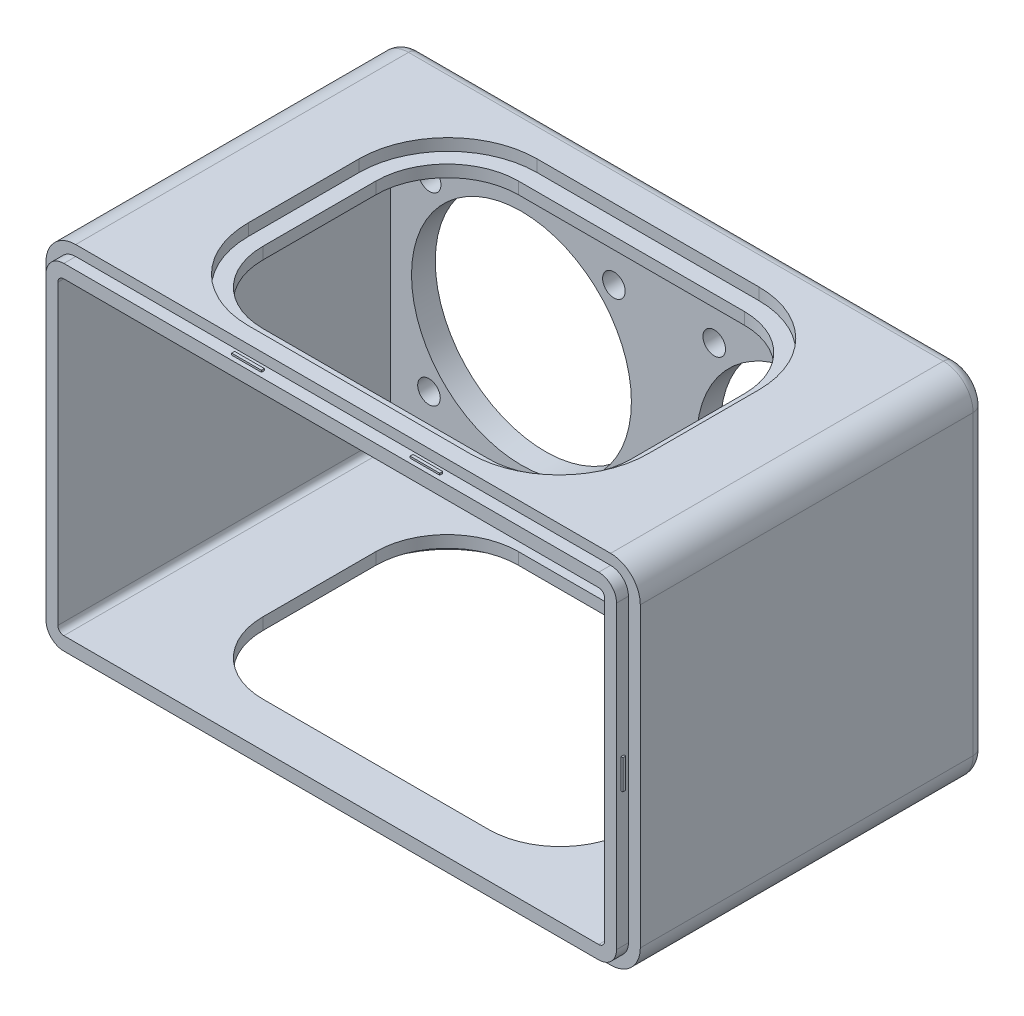
SolidWorks part; units mm, degrees
ref_plane "前视基准面" through (0, 0, 0) normal (0, 0, 1) x (1, 0, 0)
ref_plane "上视基准面" through (0, 0, 0) normal (0, 1, 0) x (1, 0, 0)
ref_plane "右视基准面" through (0, 0, 0) normal (1, 0, 0) x (0, 0, -1)
other "Configuration Table"
sketch "草图1" plane through (0, 0, 0) normal (0, 0, 1) x (1, 0, 0)
  line L0 (0, 0.156) -> (-70, 0.156) construction
  line L6 (-50, 30) -> (50, 30)
  line L11 (-50, 30) -> (-50, -30)
  line L12 (-50, -30) -> (50, -30)
  line L13 (50, 30) -> (50, -30)
  line L22 (-50, 30) -> (50, -30) construction
  line L23 (-50, -30) -> (50, 30) construction
  point P0 (0, 0)
  point P1 (0, 0)
  point P18 (0, 0)
  point P41 (0, 0)
  dimension "D1" = 100
  dimension "D2" = 60
extrude "凸台-拉伸2" add sketch "草图1" along normal blind 60
fillet "圆角1" radius 5 4 edges at (50, -30, 30) (50, 30, 30) (-50, 30, 30) (-50, -30, 30)
shell "抽壳2" thickness 4 removed face at (0, 0, 60)
fillet "圆角3" radius 2 8 edges at (48.5355, 28.5355, 0) (50, 0, 0) (48.5355, -28.5355, 0) (0, -30, 0) (-48.5355, -28.5355, 0) (-50, 0, 0) (-48.5355, 28.5355, 0) (0, 30, 0)
sketch "草图2" plane through (0, 0, 0) normal (0, 0, -1) x (-1, 0, 0)
  line L0 (0, -0.1613) -> (-48, -0.1613) construction
  circle A0 centre (-24, -0.1613) radius 18.5
  circle A1 centre (24, -0.1613) radius 18.5
  dimension "D1" = 37
  dimension "D2" = 37
  dimension "D3" = 24
  dimension "D4" = 24
extrude "切除-拉伸1" cut sketch "草图2" against normal up to next
sketch "草图3" plane through (0, -30, 0) normal (0, -1, 0) x (1, 0, 0)
  line L0 (0, 0) -> (0, 60) construction
  line L1 (-45, 60) -> (45, 60) construction
  line L2 (45, 31) -> (-45, 31) construction
  line L3 (45, 2) -> (45, 60) construction
  line L4 (-45, 60) -> (-45, 2) construction
  line L6 (19, 52.5) -> (-19, 52.5)
  line L7 (31, 40.5) -> (31, 21.5)
  line L8 (19, 9.5) -> (-19, 9.5)
  line L9 (-31, 40.5) -> (-31, 21.5)
  line L10 (31, 52.5) -> (-31, 9.5) construction
  line L11 (31, 9.5) -> (-31, 52.5) construction
  arc A0 (19, 9.5) -> (31, 21.5) centre (19, 21.5) ccw
  arc A1 (-31, 21.5) -> (-19, 9.5) centre (-19, 21.5) ccw
  arc A2 (-31, 40.5) -> (-19, 52.5) centre (-19, 40.5) cw
  arc A3 (19, 52.5) -> (31, 40.5) centre (19, 40.5) cw
  point P11 (0, 31)
  dimension "D1" = 12
extrude "切除-拉伸2" cut sketch "草图3" against normal up to surface (60 mm away) up to face at (0, 30, 31)
sketch "草图4" plane through (0, -30, 0) normal (0, -1, 0) x (1, 0, 0)
  line L0 (-45, 2) -> (45, 2) construction
  line L2 (0, 60) -> (0, 2) construction
  line L3 (18.65, 55.3) -> (-18.65, 55.3)
  line L4 (33.65, 40.3) -> (33.65, 21.7)
  line L5 (18.65, 6.7) -> (-18.65, 6.7)
  line L6 (-33.65, 40.3) -> (-33.65, 21.7)
  line L7 (33.65, 55.3) -> (-33.65, 6.7) construction
  line L8 (33.65, 6.7) -> (-33.65, 55.3) construction
  line L9 (-45, 60) -> (45, 60) construction
  arc A0 (-18.65, 6.7) -> (-33.65, 21.7) centre (-18.65, 21.7) cw
  arc A1 (-33.65, 40.3) -> (-18.65, 55.3) centre (-18.65, 40.3) cw
  arc A2 (33.65, 21.7) -> (18.65, 6.7) centre (18.65, 21.7) cw
  arc A3 (18.65, 55.3) -> (33.65, 40.3) centre (18.65, 40.3) cw
  point P5 (0, 31)
  point P24 (0, 0)
  point P25 (0, 22.1902)
  point P26 (0, 31)
  dimension "D1" = 15
  dimension "D2" = 48.6
  dimension "D3" = 67.3
extrude "切除-拉伸3" cut sketch "草图4" against normal blind 2
sketch "草图5" plane through (0, 30, 0) normal (0, 1, 0) x (1, 0, 0)
  line L0 (-33.65, -40.3) -> (-33.65, -21.7) construction
  line L1 (18.65, -6.7) -> (-18.65, -6.7) construction
  line L2 (18.65, -55.3) -> (-18.65, -55.3) construction
  line L3 (33.65, -40.3) -> (33.65, -21.7) construction
  line L4 (-33.65, -40.3) -> (-33.65, -21.7)
  line L5 (18.65, -6.7) -> (-18.65, -6.7)
  line L6 (18.65, -55.3) -> (-18.65, -55.3)
  line L7 (33.65, -40.3) -> (33.65, -21.7)
  arc A0 (-33.65, -40.3) -> (-18.65, -55.3) centre (-18.65, -40.3) ccw construction
  arc A1 (-18.65, -6.7) -> (-33.65, -21.7) centre (-18.65, -21.7) ccw construction
  arc A2 (18.65, -55.3) -> (33.65, -40.3) centre (18.65, -40.3) ccw construction
  arc A3 (33.65, -21.7) -> (18.65, -6.7) centre (18.65, -21.7) ccw construction
  arc A4 (-33.65, -40.3) -> (-18.65, -55.3) centre (-18.65, -40.3) ccw
  arc A5 (-18.65, -6.7) -> (-33.65, -21.7) centre (-18.65, -21.7) ccw
  arc A6 (18.65, -55.3) -> (33.65, -40.3) centre (18.65, -40.3) ccw
  arc A7 (33.65, -21.7) -> (18.65, -6.7) centre (18.65, -21.7) ccw
extrude "切除-拉伸4" cut sketch "草图5" against normal blind 2
sketch "草图6" plane through (0, 0, 0) normal (0, 0, -1) x (-1, 0, 0)
  line L0 (-39.5563, -15.7176) -> (-8.4437, 15.3951) construction
  line L2 (-39.5563, -15.7176) -> (-8.5563, -15.7176) construction
  line L3 (-39.4437, 15.3951) -> (-8.4437, 15.3951) construction
  line L4 (0, 0) -> (0, -28) construction
  circle A0 centre (-39.4437, 15.3951) radius 1.9
  circle A1 centre (-39.5563, -15.7176) radius 1.9
  circle A3 centre (-8.5563, -15.7176) radius 1.9
  circle A4 centre (-8.4437, 15.3951) radius 1.9
  circle A8 centre (8.5563, -15.7176) radius 1.9
  circle A9 centre (39.5563, -15.7176) radius 1.9
  circle A10 centre (8.4437, 15.3951) radius 1.9
  circle A11 centre (39.4437, 15.3951) radius 1.9
  point P21 (-24, -0.1613)
  dimension "D1" = 3.8
  dimension "D5" = 3.8
  dimension "D6" = 3.8
  dimension "D7" = 3.8
  dimension "D2" = 44
  dimension "D3" = 31
  dimension "D4" = 31
extrude "切除-拉伸5" cut sketch "草图6" against normal up to next
sketch "草图7" plane through (0, 0, 60) normal (0, 0, 1) x (1, 0, 0)
  line L1 (45, 28.25) -> (-45, 28.25)
  line L2 (48, 25.25) -> (48, -25.25)
  line L3 (45, -28.25) -> (-45, -28.25)
  line L4 (-48, 25.25) -> (-48, -25.25)
  line L5 (48, 28.25) -> (-48, -28.25) construction
  line L6 (48, -28.25) -> (-48, 28.25) construction
  arc A0 (45, -28.25) -> (48, -25.25) centre (45, -25.25) ccw
  arc A1 (-48, -25.25) -> (-45, -28.25) centre (-45, -25.25) ccw
  arc A2 (-45, 28.25) -> (-48, 25.25) centre (-45, 25.25) ccw
  arc A3 (45, 28.25) -> (48, 25.25) centre (45, 25.25) cw
  point P0 (0, 0)
  dimension "D3" = 3
  dimension "D1" = 56.5
  dimension "D2" = 96
extrude "切除-拉伸6" cut sketch "草图7" against normal blind 2 flip side to cut
sketch "草图8" plane through (0, -28.25, 0) normal (0, -1, 0) x (1, 0, 0)
  line L0 (-45, 58) -> (-45, 60) construction
  line L1 (-45, 59) -> (45, 59) construction
  line L2 (45, 58) -> (45, 60) construction
  line L4 (12.5, 59.25) -> (17.5, 59.25)
  line L5 (12.5, 59.25) -> (12.5, 58.75)
  line L6 (12.5, 58.75) -> (17.5, 58.75)
  line L7 (17.5, 59.25) -> (17.5, 58.75)
  line L8 (12.5, 59.25) -> (17.5, 58.75) construction
  line L9 (12.5, 58.75) -> (17.5, 59.25) construction
  line L22 (-17.5, 59.25) -> (-12.5, 59.25)
  line L23 (-17.5, 59.25) -> (-17.5, 58.75)
  line L24 (-17.5, 58.75) -> (-12.5, 58.75)
  line L25 (-12.5, 59.25) -> (-12.5, 58.75)
  line L26 (-17.5, 59.25) -> (-12.5, 58.75) construction
  line L27 (-17.5, 58.75) -> (-12.5, 59.25) construction
  point P6 (15, 59)
  point P12 (-15, 59)
  point P17 (0, 0)
  point P18 (-32.8362, 59)
  dimension "D1" = 30
  dimension "D2" = 0.5
  dimension "D3" = 5
  dimension "D4" = 60
extrude "凸台-拉伸3" add sketch "草图8" along normal blind 0.3
sketch "草图9" plane through (0, 28.25, 0) normal (0, 1, 0) x (1, 0, 0)
  line L0 (-17.5, -59.25) -> (-12.5, -59.25) construction
  line L1 (-12.5, -59.25) -> (-12.5, -58.75) construction
  line L2 (-17.5, -58.75) -> (-12.5, -58.75) construction
  line L3 (-17.5, -59.25) -> (-17.5, -58.75) construction
  line L4 (12.5, -59.25) -> (12.5, -58.75) construction
  line L5 (17.5, -59.25) -> (17.5, -58.75) construction
  line L6 (12.5, -58.75) -> (17.5, -58.75) construction
  line L7 (12.5, -59.25) -> (17.5, -59.25) construction
  line L8 (-17.5, -59.25) -> (-12.5, -59.25)
  line L9 (-12.5, -59.25) -> (-12.5, -58.75)
  line L10 (-17.5, -58.75) -> (-12.5, -58.75)
  line L11 (-17.5, -59.25) -> (-17.5, -58.75)
  line L12 (12.5, -59.25) -> (12.5, -58.75)
  line L13 (17.5, -59.25) -> (17.5, -58.75)
  line L14 (12.5, -58.75) -> (17.5, -58.75)
  line L15 (12.5, -59.25) -> (17.5, -59.25)
extrude "凸台-拉伸4" add sketch "草图9" along normal blind 0.3
sketch "草图10" plane through (48, 0, 0) normal (1, 0, 0) x (0, 0, -1)
  line L0 (-59, -25.25) -> (-59, 25.25) construction
  line L1 (-59.25, -2.5) -> (-58.75, -2.5)
  line L2 (-59.25, -2.5) -> (-59.25, 2.5)
  line L3 (-59.25, 2.5) -> (-58.75, 2.5)
  line L4 (-58.75, -2.5) -> (-58.75, 2.5)
  line L5 (-59.25, -2.5) -> (-58.75, 2.5) construction
  line L6 (-59.25, 2.5) -> (-58.75, -2.5) construction
  line L7 (-58, -25.25) -> (-60, -25.25) construction
  line L8 (-58, 25.25) -> (-60, 25.25) construction
  point P0 (-59, 0)
  point P11 (-59, 0)
extrude "凸台-拉伸5" add sketch "草图10" along normal blind 0.3
sketch "草图11" plane through (-48, 0, 0) normal (-1, 0, 0) x (0, 0, 1)
  line L0 (59.25, -2.5) -> (58.75, -2.5) construction
  line L1 (59.25, -2.5) -> (59.25, 2.5) construction
  line L2 (59.25, 2.5) -> (58.75, 2.5) construction
  line L3 (58.75, -2.5) -> (58.75, 2.5) construction
  line L4 (59.25, -2.5) -> (58.75, -2.5)
  line L5 (59.25, -2.5) -> (59.25, 2.5)
  line L6 (59.25, 2.5) -> (58.75, 2.5)
  line L7 (58.75, -2.5) -> (58.75, 2.5)
extrude "凸台-拉伸6" add sketch "草图11" along normal blind 0.3
